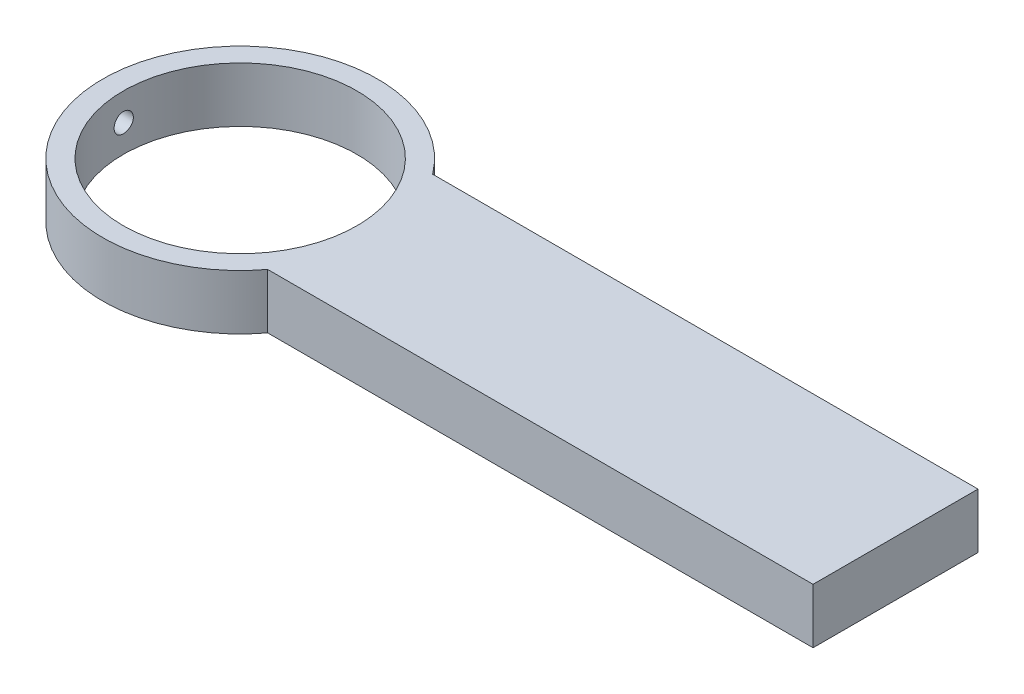
SolidWorks part; units mm, degrees
ref_plane "Front Plane" through (0, 0, 0) normal (0, 0, 1) x (1, 0, 0)
ref_plane "Top Plane" through (0, 0, 0) normal (0, 1, 0) x (1, 0, 0)
ref_plane "Right Plane" through (0, 0, 0) normal (1, 0, 0) x (0, 0, -1)
sketch "Sketch1" plane through (0, 0, 0) normal (0, 1, 0) x (1, 0, 0)
  line L0 (0, 0) -> (238.3831, 0) construction
  line L1 (40, -30) -> (238.3831, -30)
  line L2 (40, 30) -> (238.3831, 30)
  line L3 (238.3831, -30) -> (238.3831, 30)
  circle A0 centre (0, 0) radius 42.5
  circle A1 centre (0, 0) radius 50
extrude "Boss-Extrude1" add sketch "Sketch1" along normal blind 10 and the other way blind 10 contours A0 A1 | A1 L0 L3 L2 | L0 A1 L1 L3 region at (46.0925, 0, 15.3642) region at (142.5754, 0, -15.1274) region at (142.5754, 0, 15.1274)
ref_plane "Plane1" through (42.5, 0, 0) normal (-1, 0, 0) x (0, 0, 1)
sketch "Sketch2" plane through (42.5, 0, 0) normal (-1, 0, 0) x (0, 0, 1)
  circle A0 centre (0, 0) radius 3.5
ref_plane "Plane2" through (52.5, 0, 0) normal (-1, 0, 0) x (0, 0, 1)
sketch "Sketch3" plane through (52.5, 0, 0) normal (-1, 0, 0) x (0, 0, 1)
  circle A0 centre (0, 0) radius 3.5
extrude "Cut-Extrude6" cut sketch "Sketch3" along normal up to surface (10.1444 mm away) up to face at (0, -10, 42.5)
mirror "Mirror1" about plane through (0, 0, 0) normal (1, 0, 0) of "Cut-Extrude6"
